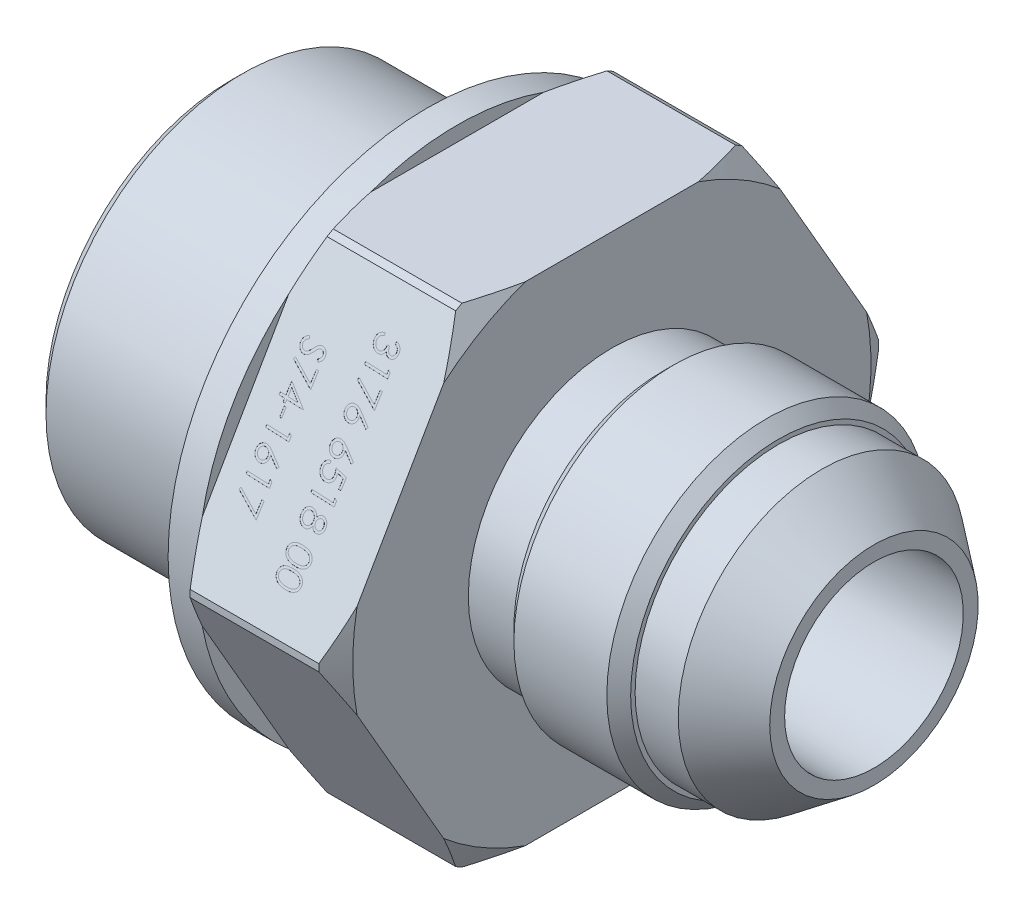
SolidWorks part; units mm, degrees
material "4140 H/T"
ref_plane "Front Plane" through (0, 0, 0) normal (0, 0, 1) x (1, 0, 0)
ref_plane "Top Plane" through (0, 0, 0) normal (0, 1, 0) x (1, 0, 0)
ref_plane "Right Plane" through (0, 0, 0) normal (1, 0, 0) x (0, 0, -1)
sketch "Sketch1" plane through (0, 0, 0) normal (0, 0, 1) x (1, 0, 0)
  line L0 (0, 0) -> (53.9967, 0) construction
  line L1 (0, 13.5) -> (0, 16.5)
  line L2 (14.25, 16.5) -> (16, 14.75)
  line L3 (0, 16.5) -> (14.25, 16.5)
  line L4 (19, 14.75) -> (19, 18.5)
  line L5 (20.1, 23.5) -> (30.9, 23.5)
  line L6 (32, 21.75) -> (32, 12.05)
  line L7 (32, 12.05) -> (36.2, 12.05)
  line L8 (36.2, 12.05) -> (36.2, 13.425)
  line L9 (36.2, 13.425) -> (46, 13.425)
  line L10 (46, 13.425) -> (46, 12.05)
  line L11 (46, 12.05) -> (49.6208, 12.05)
  line L12 (49.6208, 12.05) -> (54, 8.75)
  line L13 (54, 8.75) -> (54, 7.5)
  line L14 (22.5, 11) -> (4.3301, 11)
  line L15 (19, 21.75) -> (16.5, 21.75)
  line L16 (16.5, 21.75) -> (16.5, 18.5)
  line L17 (16.5, 18.5) -> (19, 18.5)
  line L18 (4.3301, 11) -> (0, 13.5)
  line L19 (16, 14.75) -> (19, 14.75)
  line L20 (20.1, 23.5) -> (19, 21.75)
  line L21 (30.9, 23.5) -> (32, 21.75)
  line L22 (22.5, 11) -> (24.603, 7.5)
  line L23 (24.603, 7.5) -> (54, 7.5)
  dimension "D2" = 22
  dimension "D3" = 24.1
  dimension "D4" = 37
  dimension "D5" = 8
  dimension "D6" = 26.85
  dimension "D7" = 17.8
  dimension "D8" = 19
  dimension "D9" = 22
  dimension "D10" = 54
  dimension "D11" = 33
  dimension "D12" = 3
  dimension "D13" = 47
  dimension "D14" = 43.5
  dimension "D15" = 1.1
  dimension "D16" = 1.1
  dimension "D17" = 29.5
  dimension "D18" = 2.5
  dimension "D19" = 37
  dimension "D20" = 17.5
  dimension "D21" = 45
  dimension "D22" = 27
  dimension "D24" = 30
  dimension "D23" = 15
  dimension "D25" = 59
  dimension "D26" = 22.5
revolve "Revolve1" add sketch "Sketch1" angle 360 about L0
cosmetic thread "Cosmetic Thread1" parameters "D2"=30.5
cosmetic thread "Cosmetic Thread2" parameters "D2"=24.9
sketch "Sketch2" plane through (32, 0, 0) normal (1, 0, 0) x (0, 0, -1)
  line L1 (11.8357, 20.5) -> (-11.8357, 20.5)
  line L2 (-11.8357, 20.5) -> (-23.6714, 0)
  line L3 (-23.6714, 0) -> (-11.8357, -20.5)
  line L4 (-11.8357, -20.5) -> (11.8357, -20.5)
  line L5 (11.8357, -20.5) -> (23.6714, 0)
  line L6 (23.6714, 0) -> (11.8357, 20.5)
  circle A0 centre (0, 0) radius 20.5 construction
  dimension "D1" = 41
extrude "Extrude1" cut sketch "Sketch2" against normal up to surface (13 mm away) flip side to cut up to face at (19, 0, 14.75)
chamfer "Chamfer1" distance 1 angle 45 1 edges at (0, 0, 16.5)
chamfer "Chamfer2" distance 1 angle 45 2 edges at (46, 0, 13.425) (36.2, 0, 13.425)
sketch "Sketch4" plane through (0, 0, 0) normal (0, 0, 1) x (1, 0, 0)
  line L0 (0, 0) -> (48.9759, 0) construction
  line L1 (19, 16.5436) -> (19, 20.5) construction
  circle A0 centre (17.25, 16.75) radius 1.75
  dimension "D1" = 3.5
  dimension "D3" = 33.5
revolve "Revolve2" add sketch "Sketch4" angle 360 about L0
sketch "Sketch5" plane through (0, 10.25, 17.7535) normal (0, 0.5, 0.866) x (1, 0, 0)
  line L0 (26.2345, 11.4712) -> (25.5, -11.8357) construction
  line L1 (20.2077, -11.8357) -> (30.7923, -11.8357) construction
  text T0 "3176 6518 00\r\nS74-1617" font "Century Gothic" height 2
extrude "Cut-Extrude1" cut sketch "Sketch5" against normal blind 0.01
